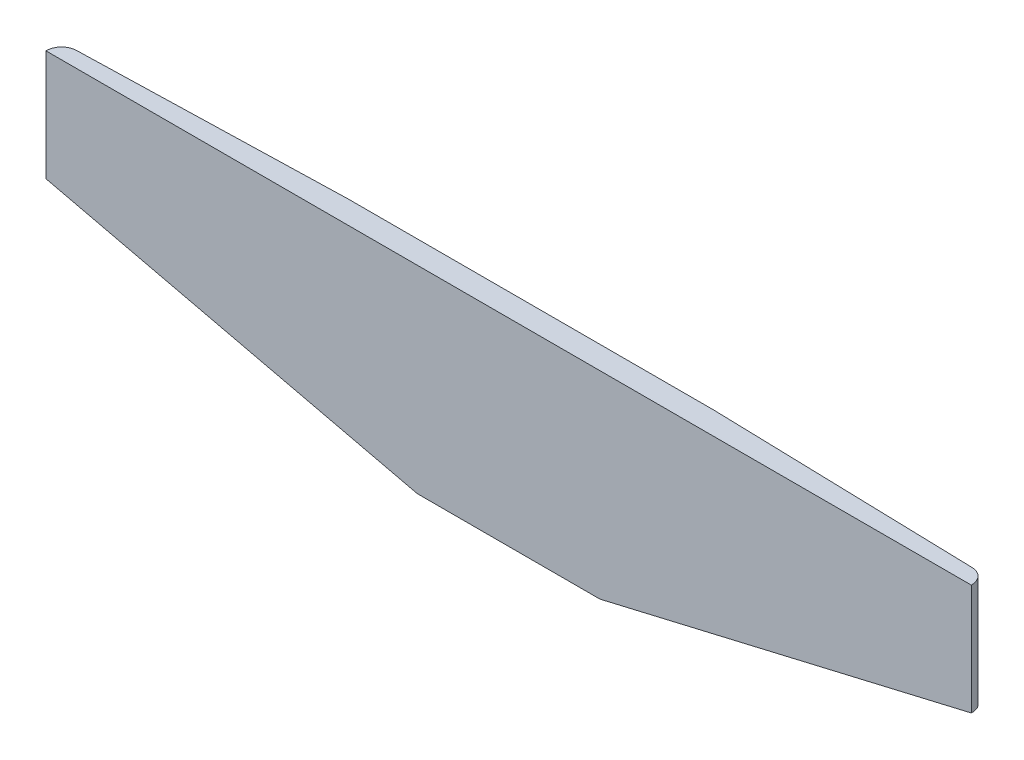
SolidWorks part; units mm, degrees
material "Alloy Steel"
ref_plane "Front Plane" through (0, 0, 0) normal (0, 0, 1) x (1, 0, 0)
ref_plane "Top Plane" through (0, 0, 0) normal (0, 1, 0) x (1, 0, 0)
ref_plane "Right Plane" through (0, 0, 0) normal (1, 0, 0) x (0, 0, -1)
sketch "Sketch1" plane through (0, 0, 0) normal (0, 0, 1) x (1, 0, 0)
  line L0 (193.04, 0) -> (193.04, -82.55) construction
  line L1 (0, 0) -> (386.08, 0)
  line L2 (0, 0) -> (0, -46.228)
  line L3 (0, -46.228) -> (386.08, -46.228) construction
  line L4 (386.08, 0) -> (386.08, -46.228)
  line L5 (154.94, -46.228) -> (231.14, -46.228) construction
  line L6 (154.94, -46.228) -> (154.94, -82.55) construction
  line L7 (154.94, -82.55) -> (231.14, -82.55)
  line L8 (231.14, -46.228) -> (231.14, -82.55) construction
  line L9 (154.94, -82.55) -> (0, -46.228)
  line L10 (231.14, -82.55) -> (386.08, -46.228)
  dimension "D1" = 386.08
  dimension "D2" = 46.228
  dimension "D3" = 76.2
  dimension "D4" = 82.55
sketch "Sketch2" plane through (0, 0, 0) normal (0, 1, 0) x (1, 0, 0)
  line L0 (0, 0) -> (386.08, 0) construction
  line L1 (0, 0) -> (386.08, 0)
  line L2 (386.08, 0) -> (386.08, 6.35)
  line L3 (0, 6.35) -> (116.84, 9.525)
  line L4 (386.08, 6.35) -> (269.24, 9.525)
  line L5 (269.24, 9.525) -> (116.84, 9.525)
  line L6 (193.04, 0) -> (193.04, 9.525)
  line L7 (0, 0) -> (0, 6.35)
  dimension "D1" = 6.35
  dimension "D2" = 76.2
  dimension "D3" = 9.525
extrude "Boss-Extrude1" add sketch "Sketch2" against normal up to vertex (82.55 mm away) contours L6 L1 L2 L4 L5 | L7 L1 L6 L5 L3 region at (102.9794, 0, -4.3469) region at (283.1006, 0, -4.3469) up to point (193.04, -82.55, 0)
extrude "Cut-Extrude1" cut sketch "Sketch1" against normal through all flip side to cut
fillet "Fillet2" radius 6.35 1 edges at (386.08, -23.114, -6.35) type face fillet first side face at (386.08, -23.114, -3.175) second side face at (327.66, -29.9616, -7.9375)
fillet "Fillet3" radius 6.35 1 edges at (0, -23.114, -6.35) type face fillet first side face at (0, -23.114, -3.175) second side face at (58.42, -29.9616, -7.9375)
